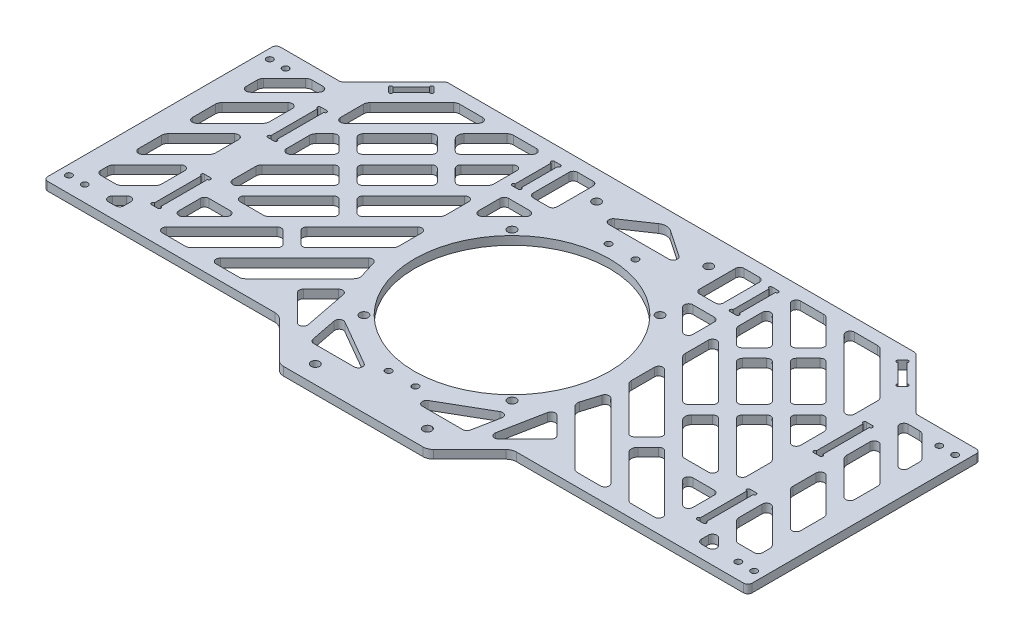
SolidWorks part; units mm, degrees
material "Thornel Mat VMA"
ref_plane "前视基准面" through (0, 0, 0) normal (0, 0, 1) x (1, 0, 0)
ref_plane "上视基准面" through (0, 0, 0) normal (0, 1, 0) x (1, 0, 0)
ref_plane "右视基准面" through (0, 0, 0) normal (1, 0, 0) x (0, 0, -1)
sketch "草图1" plane through (0, 0, 0) normal (0, 1, 0) x (1, 0, 0)
  line L0 (-55, -55) -> (-35, -75)
  line L1 (-35, -75) -> (35, -75)
  line L6 (0, -2.2) -> (0, 2.2) construction
  line L7 (-26.5, 66.5) -> (26.5, 66.5) construction
  line L8 (-26.5, 66.5) -> (-26.5, -66.5) construction
  line L9 (-26.5, -66.5) -> (26.5, -66.5) construction
  line L10 (26.5, 66.5) -> (26.5, -66.5) construction
  line L11 (55, -55) -> (35, -75)
  line L19 (-166.5, -55) -> (-55, -55)
  line L20 (-166.5, 55) -> (-166.5, -55)
  line L21 (166.5, 55) -> (166.5, -55)
  line L22 (166.5, -55) -> (55, -55)
  line L24 (-130.5, 40) -> (-127.5, 40)
  line L25 (-130.5, 40) -> (-130.5, 15)
  line L26 (-130.5, 15) -> (-127.5, 15)
  line L27 (-127.5, 40) -> (-127.5, 15)
  line L30 (130.5, -40) -> (127.5, -40)
  line L31 (130.5, -15) -> (130.5, -40)
  line L32 (127.5, -15) -> (130.5, -15)
  line L33 (127.5, -40) -> (127.5, -15)
  line L34 (127.5, 40) -> (127.5, 15)
  line L35 (-127.5, -40) -> (-127.5, -15)
  line L36 (-127.5, -15) -> (-130.5, -15)
  line L37 (-130.5, -15) -> (-130.5, -40)
  line L38 (-130.5, -40) -> (-127.5, -40)
  line L39 (130.5, 15) -> (127.5, 15)
  line L40 (130.5, 40) -> (130.5, 15)
  line L41 (130.5, 40) -> (127.5, 40)
  line L44 (135.9895, 55) -> (166.5, 55)
  line L46 (-166.5, 55) -> (-135.9895, 55)
  line L47 (-154.5, -47.5) -> (-162, -47.5) construction
  line L48 (-154.5, -47.5) -> (-154.5, 47.5) construction
  line L49 (-154.5, 47.5) -> (-162, 47.5) construction
  line L50 (-162, -47.5) -> (-162, 47.5) construction
  line L51 (-135.9895, 55) -> (-110.9895, 80)
  line L52 (-110.9895, 80) -> (110.9895, 80)
  line L56 (135.9895, 55) -> (110.9895, 80)
  line L57 (-166.5, 0) -> (0, 0) construction
  line L58 (-130.5, 15) -> (-130.5, -15) construction
  circle A0 centre (0, 0) radius 46.1
  circle A3 centre (-26.5, 66.5) radius 2
  circle A5 centre (26.5, 66.5) radius 2
  circle A6 centre (26.5, -66.5) radius 2
  circle A7 centre (-26.5, -66.5) radius 2
  circle A8 centre (-162, 47.5) radius 1.5
  circle A9 centre (-154.5, 47.5) radius 1.5
  circle A10 centre (-154.5, -47.5) radius 1.5
  circle A11 centre (-162, -47.5) radius 1.5
  circle A12 centre (154.5, -47.5) radius 1.5
  circle A13 centre (162, -47.5) radius 1.5
  circle A14 centre (154.5, 47.5) radius 1.5
  circle A15 centre (162, 47.5) radius 1.5
  point P4 (0, -75)
  point P10 (-26.5, 0)
  point P11 (0, 66.5)
  point P13 (-130.5, 0)
  dimension "D1" = 92.2
  dimension "D8" = 4
  dimension "D9" = 70
  dimension "D15" = 135
  dimension "D14" = 7.5
  dimension "D26" = 3
  dimension "D3" = 75
  dimension "D4" = 80
  dimension "D6" = 53
  dimension "D7" = 133
  dimension "D10" = 135
  dimension "D12" = 333
  dimension "D16" = 135.05
  dimension "D17" = 3
  dimension "D18" = 25
  dimension "D19" = 30
  dimension "D20" = 127.5
  dimension "D22" = 4.5
  dimension "D23" = 7.5
  dimension "D24" = 95
  dimension "D25" = 7.5
extrude "凸台-拉伸1" add sketch "草图1" along normal blind 4
sketch "草图2" plane through (0, 4, 0) normal (0, 1, 0) x (1, 0, 0)
  line L0 (0, -2.2) -> (0, 2.2) construction
  line L1 (53, 53) -> (53, 73)
  line L2 (0, 21.0132) -> (0, 0) construction
  line L3 (0, 0) -> (21.2014, 0) construction
  line L4 (-35.0018, 35.0018) -> (0, 0) construction
  line L5 (-50, 53) -> (-53, 53)
  line L6 (-50, 53) -> (-50, 73)
  line L7 (-50, 73) -> (-53, 73)
  line L8 (-53, 53) -> (-53, 73)
  line L9 (50, 73) -> (53, 73)
  line L10 (50, 53) -> (50, 73)
  line L11 (50, 53) -> (53, 53)
  line L12 (-127.5, 40) -> (-127.5, 55.0043) construction
  line L14 (-127.5, 55.0043) -> (-120.4289, 62.0753) construction
  line L15 (111.8022, 74.9447) -> (109.6809, 72.8234)
  line L16 (122.5503, 64.1966) -> (111.8022, 74.9447)
  line L17 (120.4289, 62.0753) -> (122.5503, 64.1966)
  line L18 (120.4289, 62.0753) -> (109.6809, 72.8234)
  line L19 (-2.2, 0) -> (2.2, 0) construction
  line L21 (-120.4289, 62.0753) -> (-109.6809, 72.8234)
  line L22 (-120.4289, 62.0753) -> (-122.5503, 64.1966)
  line L23 (-122.5503, 64.1966) -> (-111.8022, 74.9447)
  line L24 (-111.8022, 74.9447) -> (-109.6809, 72.8234)
  line L25 (-110.9895, 80) -> (-135.9895, 55) construction
  circle A7 centre (-35.0018, 35.0018) radius 2
  circle A9 centre (35.0018, 35.0018) radius 2
  circle A18 centre (0, 0) radius 49.5 construction
  circle A21 centre (35.0018, -35.0018) radius 2
  circle A23 centre (-35.0018, -35.0018) radius 2
  circle A24 centre (-6.35, 52) radius 1.5
  circle A26 centre (6.35, 52) radius 1.5
  circle A27 centre (6.35, -52) radius 1.5
  circle A28 centre (-6.35, -52) radius 1.5
  dimension "D1" = 99
  dimension "D2" = 4
  dimension "D3" = 100
  dimension "D8" = 3
  dimension "D10" = 3
  dimension "D11" = 3
  dimension "D9" = 10
  dimension "D13" = 12.7
  dimension "D14" = 104
  dimension "D4" = 3
  dimension "D5" = 53
  dimension "D6" = 20
  dimension "D7" = 45
  dimension "D12" = 15.2
extrude "切除-拉伸1" cut sketch "草图2" against normal through all
sketch "草图3" plane through (0, 4, 0) normal (0, 1, 0) x (1, 0, 0)
  line L0 (-53, 73) -> (-53, 53) construction
  line L1 (-50, 53) -> (-50, 73) construction
  line L2 (0, -2.2) -> (0, 2.2) construction
  line L3 (-111.8022, 74.9447) -> (-122.5503, 64.1966) construction
  line L4 (-120.4289, 62.0753) -> (-109.6809, 72.8234) construction
  line L5 (-130.5, 40) -> (-130.5, 15) construction
  line L6 (-127.5, 15) -> (-127.5, 40) construction
  line L7 (-130.5, -15) -> (-130.5, -40) construction
  line L8 (-127.5, -40) -> (-127.5, -15) construction
  circle A0 centre (-53, 72.25) radius 0.75
  circle A1 centre (-50, 72.25) radius 0.75
  circle A2 centre (-50, 53.75) radius 0.75
  circle A3 centre (-53, 53.75) radius 0.75
  circle A4 centre (53, 53.75) radius 0.75
  circle A5 centre (50, 53.75) radius 0.75
  circle A6 centre (50, 72.25) radius 0.75
  circle A7 centre (53, 72.25) radius 0.75
  circle A8 centre (-112.3326, 74.4143) radius 0.75
  circle A9 centre (-122.0199, 64.727) radius 0.75
  circle A10 centre (-119.8986, 62.6057) radius 0.75
  circle A11 centre (-110.2112, 72.293) radius 0.75
  circle A12 centre (-130.5, 39.25) radius 0.75
  circle A13 centre (-127.5, 39.25) radius 0.75
  circle A14 centre (-127.5, 15.75) radius 0.75
  circle A15 centre (-130.5, 15.75) radius 0.75
  circle A16 centre (-130.5, -15.75) radius 0.75
  circle A17 centre (-127.5, -15.75) radius 0.75
  circle A18 centre (-127.5, -39.25) radius 0.75
  circle A19 centre (-130.5, -39.25) radius 0.75
  circle A20 centre (130.5, -39.25) radius 0.75
  circle A21 centre (127.5, -39.25) radius 0.75
  circle A22 centre (127.5, -15.75) radius 0.75
  circle A23 centre (130.5, -15.75) radius 0.75
  circle A24 centre (130.5, 15.75) radius 0.75
  circle A25 centre (127.5, 15.75) radius 0.75
  circle A26 centre (127.5, 39.25) radius 0.75
  circle A27 centre (130.5, 39.25) radius 0.75
  circle A28 centre (110.2112, 72.293) radius 0.75
  circle A29 centre (119.8986, 62.6057) radius 0.75
  circle A30 centre (122.0199, 64.727) radius 0.75
  circle A31 centre (112.3326, 74.4143) radius 0.75
  dimension "D1" = 1.5
extrude "切除-拉伸2" cut sketch "草图3" against normal through all
sketch "草图12" plane through (0, 4, 0) normal (0, 1, 0) x (1, 0, 0)
  line L0 (-136.5, -13.3927) -> (-136.5, -30.3633)
  line L3 (-136.5, 12.0631) -> (-136.5, -4.9074)
  line L4 (-156.5, 17.519) -> (-156.5, 0.5484)
  line L5 (-156.5, -7.9369) -> (-156.5, -24.9074)
  line L6 (-156.5, -33.3927) -> (-156.5, -40)
  line L9 (-136.5, -38.8486) -> (-146.6514, -49)
  line L10 (-146.6514, -49) -> (-136.5, -49)
  line L11 (-100.019, 74) -> (-121.5, 52.519)
  line L30 (-121.5, 52.519) -> (-121.5, 35.5484)
  line L31 (-100.019, 74) -> (-83.0484, 74)
  line L32 (-136.5, -49) -> (-136.5, -38.8486)
  line L33 (-83.0484, 74) -> (-121.5, 35.5484)
  line L34 (-74.5631, 74) -> (-57.5926, 74)
  line L38 (-57.5926, 74) -> (-121.5, 10.0926)
  line L39 (-74.5631, 74) -> (-121.5, 27.0631)
  line L40 (-58, 65.1073) -> (-58, 48.1367)
  line L41 (-144.818, 49) -> (-156.5, 37.318)
  line L42 (-58, 65.1073) -> (-121.5, 1.6073)
  line L43 (-121.5, -15.3633) -> (-58, 48.1367)
  line L44 (-119.3683, 63.136) -> (-110.7416, 71.7627) construction
  line L66 (-50.6514, 47) -> (-33.6809, 47)
  line L69 (-33.6809, 47) -> (-121.5, -40.8191)
  line L72 (-50.6514, 47) -> (-121.5, -23.8486)
  line L73 (110.9895, 80) -> (-110.9895, 80) construction
  line L74 (-127.5, 16.5) -> (-127.5, 38.5) construction
  line L75 (-53, 71.5) -> (-53, 54.5) construction
  line L76 (-53, 53) -> (-50, 53) construction
  line L77 (-102.2742, 54.7742) -> (-98.0316, 50.5316) construction
  line L78 (-89.5463, 42.0463) -> (-85.3036, 37.8036) construction
  line L79 (-89.75, 16.3867) -> (-85.5074, 12.1441) construction
  line L80 (-121.1956, -49) -> (-55, 17.1956)
  line L81 (-55, 17.1956) -> (-55, 0.225)
  line L82 (-55, 0.225) -> (-104.225, -49)
  line L83 (-104.225, -49) -> (-121.1956, -49)
  line L84 (-88.0978, -15.9022) -> (-92.3404, -11.6596) construction
  line L85 (-166.5, -55) -> (-55, -55) construction
  line L86 (-121.5, 27.0631) -> (-121.5, 10.0926)
  line L87 (-121.5, 1.6073) -> (-121.5, -15.3633)
  line L88 (-121.5, -23.8486) -> (-121.5, -40.8191)
  line L89 (-55, -8.2602) -> (-95.7398, -49)
  line L90 (-95.7398, -49) -> (-78.7692, -49)
  line L91 (-78.7692, -49) -> (-51.0108, -21.2416)
  line L92 (-51.0108, -21.2416) -> (-55, -8.2602)
  line L93 (-49.0162, -27.7323) -> (-61.3993, -40.1154)
  line L94 (-61.3993, -40.1154) -> (-43.0147, -58.5)
  line L95 (-43.0147, -58.5) -> (-49.0162, -27.7323)
  line L96 (-55, -55) -> (-35, -75) construction
  line L97 (-79.6125, -24.3875) -> (-75.3699, -28.6301) construction
  line L99 (-55.2077, -33.9238) -> (-59.4504, -29.6812) construction
  line L100 (-20.6809, 60) -> (0, 74)
  line L101 (-20.6809, 60) -> (20.6809, 60)
  line L102 (-50, 54.5) -> (-50, 71.5) construction
  line L103 (-45, 74) -> (-33.6809, 74)
  line L104 (-45, 74) -> (-45, 53)
  line L105 (-45, 53) -> (-33.6809, 53)
  line L106 (-33.6809, 74) -> (-33.6809, 53)
  line L107 (-136.5, 20.5484) -> (-156.5, 0.5484)
  line L108 (-144.818, 49) -> (-133.5043, 49)
  line L109 (-156.5, 37.318) -> (-156.5, 26.0043)
  line L110 (-156.5, -40) -> (-146.1367, -40)
  line L111 (-136.5, 37.519) -> (-136.5, 20.5484)
  line L112 (-136.5, 12.0631) -> (-156.5, -7.9369)
  line L113 (-136.5, -4.9074) -> (-156.5, -24.9074)
  line L114 (-156.5, -33.3927) -> (-136.5, -13.3927)
  line L115 (-136.5, -30.3633) -> (-146.1367, -40)
  line L117 (-130.5, 38.5) -> (-130.5, 16.5) construction
  line L118 (-136.5, 37.519) -> (-156.5, 17.519)
  line L119 (-135.9895, 55) -> (-166.5, 55) construction
  line L120 (-133.5043, 49) -> (-156.5, 26.0043)
  line L121 (-166.5, 55) -> (-166.5, -55) construction
  line L122 (-40.4838, -40.1352) -> (-36.9016, -58.5)
  line L123 (-36.9016, -58.5) -> (-8.675, -58.5)
  line L124 (-8.675, -58.5) -> (-40.4838, -40.1352)
  line L125 (0, -2.2) -> (0, 2.2) construction
  line L126 (55.2077, -33.9238) -> (59.4504, -29.6812) construction
  line L132 (8.675, -58.5) -> (40.4838, -40.1352)
  line L133 (36.9016, -58.5) -> (8.675, -58.5)
  line L134 (40.4838, -40.1352) -> (36.9016, -58.5)
  line L135 (133.5043, 49) -> (156.5, 26.0043)
  line L136 (136.5, 37.519) -> (156.5, 17.519)
  line L137 (136.5, -30.3633) -> (146.1367, -40)
  line L138 (156.5, -33.3927) -> (136.5, -13.3927)
  line L139 (136.5, -4.9074) -> (156.5, -24.9074)
  line L140 (136.5, 12.0631) -> (156.5, -7.9369)
  line L141 (136.5, 37.519) -> (136.5, 20.5484)
  line L142 (156.5, -40) -> (146.1367, -40)
  line L143 (156.5, 37.318) -> (156.5, 26.0043)
  line L144 (144.818, 49) -> (133.5043, 49)
  line L145 (136.5, 20.5484) -> (156.5, 0.5484)
  line L146 (33.6809, 74) -> (33.6809, 53)
  line L147 (45, 53) -> (33.6809, 53)
  line L148 (45, 74) -> (45, 53)
  line L149 (45, 74) -> (33.6809, 74)
  line L150 (20.6809, 60) -> (0, 74)
  line L151 (43.0147, -58.5) -> (49.0162, -27.7323)
  line L152 (61.3993, -40.1154) -> (43.0147, -58.5)
  line L153 (49.0162, -27.7323) -> (61.3993, -40.1154)
  line L154 (51.0108, -21.2416) -> (55, -8.2602)
  line L155 (78.7692, -49) -> (51.0108, -21.2416)
  line L156 (95.7398, -49) -> (78.7692, -49)
  line L157 (55, -8.2602) -> (95.7398, -49)
  line L158 (121.5, -23.8486) -> (121.5, -40.8191)
  line L159 (121.5, 1.6073) -> (121.5, -15.3633)
  line L160 (121.5, 27.0631) -> (121.5, 10.0926)
  line L161 (104.225, -49) -> (121.1956, -49)
  line L162 (55, 0.225) -> (104.225, -49)
  line L163 (55, 17.1956) -> (55, 0.225)
  line L164 (121.1956, -49) -> (55, 17.1956)
  line L165 (50.6514, 47) -> (121.5, -23.8486)
  line L166 (33.6809, 47) -> (121.5, -40.8191)
  line L167 (50.6514, 47) -> (33.6809, 47)
  line L168 (121.5, -15.3633) -> (58, 48.1367)
  line L169 (58, 65.1073) -> (121.5, 1.6073)
  line L170 (144.818, 49) -> (156.5, 37.318)
  line L171 (58, 65.1073) -> (58, 48.1367)
  line L172 (74.5631, 74) -> (121.5, 27.0631)
  line L173 (57.5926, 74) -> (121.5, 10.0926)
  line L174 (74.5631, 74) -> (57.5926, 74)
  line L175 (83.0484, 74) -> (121.5, 35.5484)
  line L176 (136.5, -49) -> (136.5, -38.8486)
  line L177 (100.019, 74) -> (83.0484, 74)
  line L178 (121.5, 52.519) -> (121.5, 35.5484)
  line L179 (100.019, 74) -> (121.5, 52.519)
  line L180 (146.6514, -49) -> (136.5, -49)
  line L181 (136.5, -38.8486) -> (146.6514, -49)
  line L182 (156.5, -33.3927) -> (156.5, -40)
  line L183 (156.5, -7.9369) -> (156.5, -24.9074)
  line L184 (156.5, 17.519) -> (156.5, 0.5484)
  line L185 (136.5, 12.0631) -> (136.5, -4.9074)
  line L186 (136.5, -13.3927) -> (136.5, -30.3633)
  circle A8 centre (0, 0) radius 46.1 construction
  circle A9 centre (-26.5, -66.5) radius 2 construction
  circle A10 centre (-6.35, 52) radius 1.5 construction
  point P171 (0, 60)
  dimension "D3" = 6
  dimension "D17" = 8
  dimension "D27" = 8
  dimension "D1" = 6
  dimension "D2" = 6
  dimension "D4" = 5
  dimension "D5" = 6
  dimension "D6" = 6
  dimension "D7" = 12
  dimension "D8" = 12
  dimension "D9" = 12
  dimension "D10" = 12
  dimension "D11" = 6
  dimension "D12" = 55
  dimension "D13" = 12
  dimension "D14" = 12
  dimension "D15" = 55
  dimension "D16" = 6
  dimension "D18" = 5
  dimension "D19" = 6
  dimension "D20" = 6
  dimension "D21" = 10
  dimension "D22" = 15
  dimension "D23" = 8
  dimension "D24" = 6
  dimension "D25" = 55
  dimension "D26" = 30
extrude "切除-拉伸8" cut sketch "草图12" against normal through all
sketch "草图13" plane through (0, 4, 0) normal (0, 1, 0) x (1, 0, 0)
  line L0 (-53.6514, 47) -> (-53.6514, 22.7868)
  line L2 (-88.0978, -15.9022) -> (-79.6125, -24.3875)
  line L4 (-74.5631, 74) -> (-121.5, 27.0631) construction
  line L6 (-121.5, -20.8486) -> (-97.2868, -20.8486)
  line L9 (-113.0147, 35.5484) -> (-79.0736, 1.6073)
  line L10 (-121.5, -15.3633) -> (-58, 48.1367) construction
  line L11 (-68.6066, 37.5301) -> (-89.8198, 58.7433)
  line L12 (-55, 17.1956) -> (-121.1956, -49) construction
  line L13 (-104.225, -49) -> (-55, 0.225) construction
  line L14 (-33.6809, 47) -> (-50.6514, 47) construction
  line L15 (-121.5, -23.8486) -> (-121.5, -40.8191) construction
  line L16 (0, -2.2) -> (0, 2.2) construction
  line L17 (68.6066, 37.5301) -> (89.8198, 58.7433)
  line L18 (113.0147, 35.5484) -> (79.0736, 1.6073)
  line L19 (121.5, -20.8486) -> (97.2868, -20.8486)
  line L20 (88.0978, -15.9022) -> (79.6125, -24.3875)
  line L21 (53.6514, 47) -> (53.6514, 22.7868)
  line L22 (-121.5, -40.8191) -> (-33.6809, 47) construction
  dimension "D1" = 3
  dimension "D2" = 3
  dimension "D3" = 12
  dimension "D4" = 15
  dimension "D5" = 3
  dimension "D6" = 3
extrude "拉伸-薄壁1" add sketch "草图13" against normal up to surface (4 mm away) thin up to face at (-139.8838, 0, 45.6162) thin type mid plane wall 6
fillet "圆角1" radius 5 5 edges at (35, 2, 75) (-35, 2, 75) (55, 2, 55) (-55, 2, 55) (0, 2, -74)
fillet "圆角2" radius 2 8 edges at (-166.5, 2, 55) (-135.9895, 2, -55) (-110.9895, 2, -80) (110.9895, 2, -80) (135.9895, 2, -55) (166.5, 2, -55) (166.5, 2, 55) (-166.5, 2, -55)
fillet "圆角3" radius 2 127 edges at (-110.8934, 2, -37.6697) (-91.9411, 2, -56.622) (-83.4558, 2, -48.1367) (-102.4081, 2, -29.1845) (-93.9228, 2, -12.2139) (-121.5, 2, 15.3633) (-102.4081, 2, -20.6992) (-81.1949, 2, 0.514) (-115.5, 2, 17.8486) (-89.6802, 2, -7.9713) (-79.2132, 2, -43.8941) (-70.7279, 2, -35.4088) (-89.6802, 2, -16.4565) (-98.1655, 2, -24.9418) (-56.6514, 2, -41) (-76.9523, 2, -3.7286) (-85.4376, 2, -12.2139) (-121.5, 2, -10.0926) (-115.136, 2, -33.4271) (-106.6508, 2, -24.9418) (-57.5926, 2, -74) (-79.2132, 2, -52.3794) (-58, 2, -65.1073) (-66.4853, 2, -39.6514) (-74.9706, 2, -48.1367) (-121.5, 2, -35.5484) (-83.0484, 2, -74) (156.5, 2, 40) (146.1367, 2, 40) (136.5, 2, 13.3927) (156.5, 2, 24.9074) (136.5, 2, -12.0631) (156.5, 2, -26.0043) (133.5043, 2, -49) (156.5, 2, -0.5484) (136.5, 2, -37.519) (55, 2, 8.2602) (95.7398, 2, 49) (49.0162, 2, 27.7323) (61.3993, 2, 40.1154) (43.0147, 2, 58.5) (45, 2, -53) (33.6809, 2, -53) (33.6809, 2, -74) (45, 2, -74) (136.5, 2, 38.8486) (146.6514, 2, 49) (136.5, 2, 49) (121.5, 2, -35.5484) (83.0484, 2, -74) (55, 2, -17.1956) (85.9765, 2, 13.7809) (77.4912, 2, 22.2662) (-33.6809, 2, -74) (-33.6809, 2, -53) (-45, 2, -53) (-45, 2, -74) (20.6809, 2, -60) (-20.6809, 2, -60) (-55, 2, -17.1956) (-77.4912, 2, 22.2662) (-85.9765, 2, 13.7809) (-61.3993, 2, 40.1154) (-49.0162, 2, 27.7323) (-43.0147, 2, 58.5) (-95.7398, 2, 49) (-55, 2, 8.2602) (40.4838, 2, 40.1352) (36.9016, 2, 58.5) (8.675, 2, 58.5) (-156.5, 2, -26.0043) (-133.5043, 2, -49) (-156.5, 2, 24.9074) (-136.5, 2, -12.0631) (-156.5, 2, -0.5484) (-136.5, 2, -37.519) (-36.9016, 2, 58.5) (-40.4838, 2, 40.1352) (-8.675, 2, 58.5) (-136.5, 2, 13.3927) (-156.5, 2, 40) (-146.6514, 2, 49) (-136.5, 2, 38.8486) (-136.5, 2, 49) (-33.6809, 2, -47) (-50.6514, 2, -30.0294) (-50.6514, 2, -47) (-104.5294, 2, 23.8486) (-121.5, 2, 40.8191) (-121.5, 2, 23.8486) (-81.7338, 2, 26.5088) (-121.1956, 2, 49) (-90.2191, 2, 18.0235) (66.4853, 2, -39.6514) (58, 2, -65.1073) (74.9706, 2, -48.1367) (57.5926, 2, -74) (87.6985, 2, -60.8646) (79.2132, 2, -52.3794) (83.4558, 2, -48.1367) (91.9411, 2, -56.622) (110.8934, 2, -37.6697) (102.4081, 2, -29.1845) (115.136, 2, -33.4271) (121.5, 2, -10.0926) (106.6508, 2, -24.9418) (89.6802, 2, -16.4565) (70.7279, 2, -35.4088) (79.2132, 2, -43.8941) (98.1655, 2, -24.9418) (121.5, 2, 15.3633) (93.9228, 2, -12.2139) (102.4081, 2, -20.6992) (121.5, 2, 40.8191) (104.5294, 2, 23.8486) (121.5, 2, 23.8486) (98.5294, 2, 17.8486) (89.6802, 2, -7.9713) (115.5, 2, 17.8486) (90.2191, 2, 18.0235) (121.1956, 2, 49) (50.6514, 2, -30.0294) (33.6809, 2, -47) (50.6514, 2, -47) (85.4376, 2, -12.2139) (76.9523, 2, -3.7286) (56.6514, 2, -41)
fillet "圆角4" radius 3 43 edges at (-121.5, 2, -1.6073) (-121.5, 2, -27.0631) (-74.5631, 2, -74) (-87.6985, 2, -60.8646) (-100.019, 2, -74) (-121.5, 2, -52.519) (-58, 2, -48.1367) (-56.6514, 2, -24.0294) (-55, 2, -0.225) (-51.0108, 2, 21.2416) (-78.7692, 2, 49) (-104.225, 2, 49) (-98.5294, 2, 17.8486) (-136.5, 2, -20.5484) (-136.5, 2, 4.9074) (-146.1367, 2, 40) (-136.5, 2, 30.3633) (-156.5, 2, 33.3927) (-156.5, 2, 7.9369) (-156.5, 2, -17.519) (-156.5, 2, -37.318) (-144.818, 2, -49) (78.7692, 2, 49) (104.225, 2, 49) (156.5, 2, 33.3927) (156.5, 2, 7.9369) (156.5, 2, -17.519) (156.5, 2, -37.318) (144.818, 2, -49) (136.5, 2, -20.5484) (136.5, 2, 4.9074) (136.5, 2, 30.3633) (81.1949, 2, 0.514) (81.7338, 2, 26.5088) (51.0108, 2, 21.2416) (55, 2, -0.225) (56.6514, 2, -24.0294) (58, 2, -48.1367) (121.5, 2, -1.6073) (121.5, 2, -27.0631) (121.5, 2, -52.519) (100.019, 2, -74) (74.5631, 2, -74)
